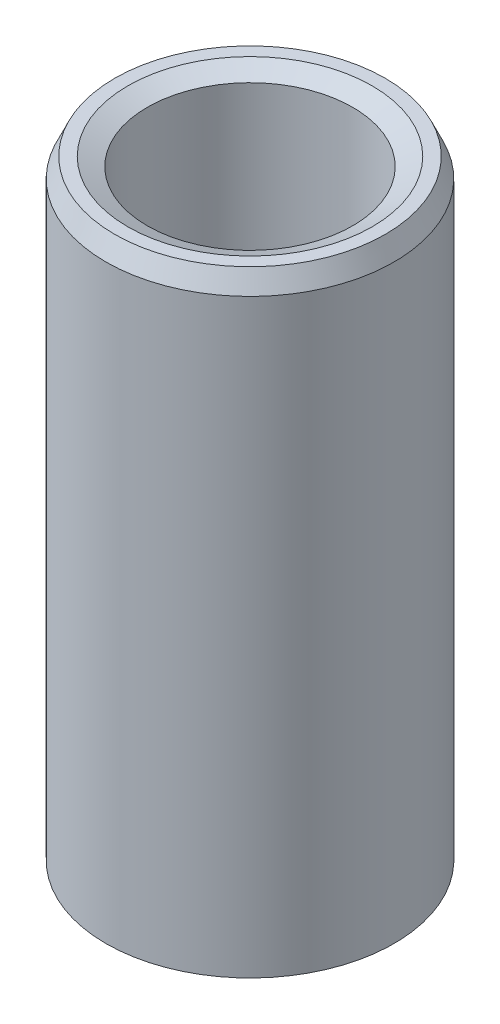
SolidWorks part; units mm, degrees
ref_plane "Front Plane" through (0, 0, 0) normal (0, 0, 1) x (1, 0, 0)
ref_plane "Top Plane" through (0, 0, 0) normal (0, 1, 0) x (1, 0, 0)
ref_plane "Right Plane" through (0, 0, 0) normal (1, 0, 0) x (0, 0, -1)
sketch "Sketch1" plane through (0, 0, 0) normal (0, 1, 0) x (1, 0, 0)
  circle A0 centre (0, 0) radius 15
  dimension "SLEEVE_OD" = 30
extrude "Boss-Extrude1" add sketch "Sketch1" along normal blind 64.3867
sketch "Sketch2" plane through (0, 0, 0) normal (0, 1, 0) x (1, 0, 0)
  circle A0 centre (0, 0) radius 10.6905
  dimension "BORE_D" = 21.381
extrude "Cut-Extrude1" cut sketch "Sketch2" along normal through all
chamfer "Chamfer1" distance 2.0249 angle 24.483 4 edges at (0, 64.3867, 10.6905) (0, 0, 10.6905) (0, 0, 15) (0, 64.3867, 15) first distance on face at (0, 64.3867, 10.6905) first distance on face at (0, 0, 10.6905) first distance on face at (0, 64.3867, 15)
